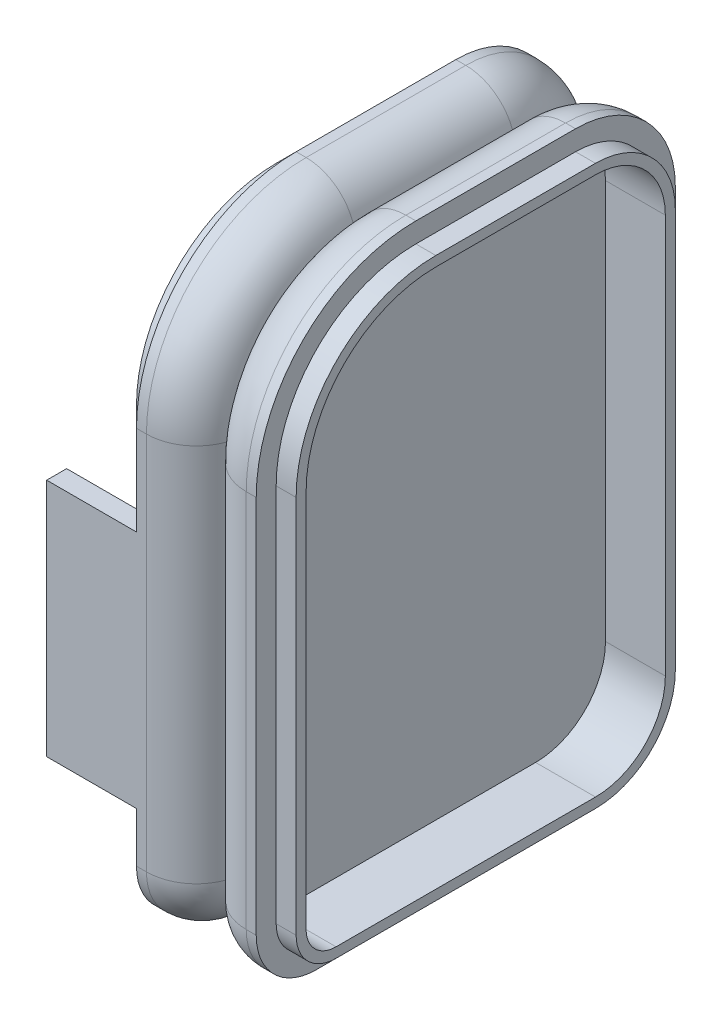
SolidWorks part; units mm, degrees
ref_plane "Спереди" through (0, 0, 0) normal (0, 0, 1) x (1, 0, 0)
ref_plane "Сверху" through (0, 0, 0) normal (0, 1, 0) x (1, 0, 0)
ref_plane "Справа" through (0, 0, 0) normal (1, 0, 0) x (0, 0, -1)
sketch "Эскиз1" plane through (0, 0, 0) normal (1, 0, 0) x (0, 0, -1)
  line L0 (2, 30) -> (40, 30) construction
  line L1 (0, 0) -> (2, 0)
  line L2 (0, 0) -> (0, 60)
  line L3 (0, 60) -> (2, 60)
  line L4 (2, 0) -> (2, 60)
  line L5 (2, 0) -> (18, 0)
  line L6 (2, 0) -> (2, 2)
  line L7 (2, 2) -> (18, 2)
  line L8 (18, 0) -> (18, 2)
  line L9 (18, 0) -> (19, 0)
  line L10 (18, 0) -> (18, 1.9)
  line L11 (18, 1.9) -> (19, 1.9)
  line L12 (19, 0) -> (19, 1.9)
  line L13 (19, 0) -> (40, 0)
  line L14 (19, 0) -> (19, 2)
  line L15 (19, 2) -> (40, 2)
  line L16 (40, 0) -> (40, 2)
  line L17 (2, 60) -> (18, 60)
  line L18 (2, 60) -> (2, 58)
  line L19 (2, 58) -> (18, 58)
  line L20 (18, 60) -> (18, 58)
  line L21 (18, 60) -> (19, 60)
  line L22 (18, 60) -> (18, 58.1)
  line L23 (18, 58.1) -> (19, 58.1)
  line L24 (19, 60) -> (19, 58.1)
  line L25 (19, 60) -> (40, 60)
  line L26 (19, 60) -> (19, 58)
  line L27 (19, 58) -> (40, 58)
  line L28 (40, 60) -> (40, 58)
  line L29 (40, 60) -> (42, 60)
  line L30 (40, 60) -> (40, 0)
  line L31 (40, 0) -> (42, 0)
  line L32 (42, 60) -> (42, 0)
  dimension "D1" = 2
  dimension "D2" = 60
  dimension "D3" = 18
  dimension "D4" = 1.9
  dimension "D5" = 1
  dimension "D6" = 21
extrude "Бобышка-Вытянуть1" add sketch "Эскиз1" against normal blind 90 contours L20 L17 L4 L19 | L24 L21 L20 L23 | L28 L25 L24 L26 L27 | L1 L4 L3 L2 | L32 L29 L28 L30 L16 L31 | L13 L16 L15 L14 L12 | L9 L12 L11 L8 | L5 L8 L7 L4 region at (0, 30, -1) region at (0, 1, -10) region at (0, 0.95, -18.5) region at (0, 59, -10) region at (0, 1, -29.5) region at (0, 59.05, -18.5) region at (0, 30, -41) region at (0, 59, -29.5)
sketch "Эскиз2" plane through (0, 0, 0) normal (1, 0, 0) x (0, 0, -1)
  line L0 (0, 0) -> (0, 60) construction
  line L1 (0, 11) -> (2, 11)
  line L2 (0, 11) -> (0, 35)
  line L3 (0, 35) -> (2, 35)
  line L4 (2, 11) -> (2, 35)
  line L5 (2, 2) -> (2, 58) construction
  line L7 (0, 0) -> (42, 0) construction
  dimension "D1" = 11
  dimension "D2" = 24
extrude "Вырез-Вытянуть1" cut sketch "Эскиз2" against normal through all
sketch "Эскиз4" plane through (-90, 0, 0) normal (-1, 0, 0) x (0, 0, 1)
  line L1 (-19, 58) -> (-18, 58)
  line L2 (-19, 58) -> (-19, 58.1)
  line L3 (-19, 58.1) -> (-18, 58.1)
  line L4 (-18, 58) -> (-18, 58.1)
  line L5 (-19, 1.9) -> (-18, 1.9)
  line L6 (-19, 1.9) -> (-19, 2)
  line L7 (-19, 2) -> (-18, 2)
  line L8 (-18, 1.9) -> (-18, 2)
extrude "Бобышка-Вытянуть2" add sketch "Эскиз4" against normal blind 3
sketch "Эскиз5" plane through (-90, 0, 0) normal (-1, 0, 0) x (0, 0, 1)
  line L1 (-2, 35) -> (0, 35)
  line L2 (-2, 35) -> (-2, 11)
  line L3 (-2, 11) -> (0, 11)
  line L4 (0, 35) -> (0, 11)
  line M1 (-2, 11) -> (-2, 2)
  line M2 (-2, 2) -> (-40, 2)
  line M3 (-40, 2) -> (-40, 58)
  line M4 (-40, 58) -> (-2, 58)
  line M5 (-2, 58) -> (-2, 35)
  line M6 (-2, 35) -> (0, 35)
  line M7 (0, 35) -> (0, 60)
  line M8 (0, 60) -> (-42, 60)
  line M9 (-42, 60) -> (-42, 0)
  line M10 (-42, 0) -> (0, 0)
  line M11 (0, 0) -> (0, 11)
  line M12 (0, 11) -> (-2, 11)
extrude "Бобышка-Вытянуть3" add sketch "Эскиз5" along normal blind 10 contours M12 M1 M2 M3 M4 M5 M6 M7 M8 M9 M10 M11 | L4 L2 M6 M12 region at (-90, 46.5, -1.2676) region at (-90, 23, -1)
sketch "Эскиз6" plane through (-100, 0, 0) normal (-1, 0, 0) x (0, 0, 1)
  line L4 (-42, 0) -> (0, 0)
  line L5 (0, 0) -> (0, 60)
  line L6 (0, 60) -> (-42, 60)
  line L7 (-42, 60) -> (-42, 0)
  line L8 (-42, 0) -> (0, 0)
  line L9 (0, 0) -> (0, 60)
  line L10 (0, 60) -> (-42, 60)
  line L11 (-42, 60) -> (-42, 0)
  dimension "D1" = 0
extrude "Бобышка-Вытянуть4" add sketch "Эскиз6" along normal blind 2
sketch "Эскиз8" plane through (0, 11, 0) normal (0, 1, 0) x (1, 0, 0)
  line L0 (-90, 2) -> (0, 2) construction
  line L1 (-90, 0) -> (-80, 0)
  line L2 (-90, 0) -> (-90, 2)
  line L3 (-90, 2) -> (-80, 2)
  line L4 (-80, 0) -> (-80, 2)
  dimension "D1" = 10
extrude "Бобышка-Вытянуть5" add sketch "Эскиз8" along normal up to next
fillet "Скругление1" radius 14 1 edges at (-50, 58, -2)
fillet "Скругление2" radius 16 1 edges at (-51, 60, 0)
fillet "Скругление4" radius 8 2 edges at (-50, 58, -40) (-50, 2, -40)
fillet "Скругление5" radius 10 2 edges at (-51, 60, -42) (-51, 0, -42)
fillet "Скругление6" radius 4 1 edges at (-50, 2, -2)
fillet "Скругление7" radius 6 1 edges at (-51, 0, 0)
fillet "Скругление8" radius 5 8 edges at (-102, 25, 0) (-102, 1.7574, -1.7574) (-102, 0, -19) (-102, 2.9289, -39.0711) (-102, 30, -42) (-102, 57.0711, -39.0711) (-102, 60, -24) (-102, 55.3137, -4.6863)
fillet "Скругление9" radius 1 8 edges at (-100, 3.1716, -3.1716) (-100, 25, -2) (-100, 53.8995, -6.1005) (-100, 58, -24) (-100, 55.6569, -37.6569) (-100, 30, -40) (-100, 4.3431, -37.6569) (-100, 2, -19)
sketch "Эскиз9" plane through (0, 0, 0) normal (1, 0, 0) x (0, 0, -1)
  line L20 (0, 11) -> (0, 6)
  line L21 (6, 0) -> (32, 0)
  line L22 (42, 10) -> (42, 50)
  line L23 (32, 60) -> (16, 60)
  line L24 (0, 44) -> (0, 35)
  line L25 (0, 35) -> (2, 35)
  line L26 (2, 35) -> (2, 44)
  line L27 (16, 58) -> (18, 58)
  line L28 (18, 58) -> (18, 58.1)
  line L29 (18, 58.1) -> (19, 58.1)
  line L30 (19, 58.1) -> (19, 58)
  line L31 (19, 58) -> (32, 58)
  line L32 (40, 50) -> (40, 10)
  line L33 (32, 2) -> (19, 2)
  line L34 (19, 2) -> (19, 1.9)
  line L35 (19, 1.9) -> (18, 1.9)
  line L36 (18, 1.9) -> (18, 2)
  line L37 (18, 2) -> (6, 2)
  line L38 (2, 6) -> (2, 11)
  line L39 (2, 11) -> (0, 11)
  line L40 (0, 11) -> (0, 6)
  line L41 (6, 0) -> (32, 0)
  line L42 (42, 10) -> (42, 50)
  line L43 (32, 60) -> (16, 60)
  line L44 (0, 44) -> (0, 35)
  line L45 (0, 35) -> (2, 35)
  line L46 (2, 35) -> (2, 44)
  line L47 (16, 58) -> (18, 58)
  line L48 (18, 58) -> (18, 58.1)
  line L49 (18, 58.1) -> (19, 58.1)
  line L50 (19, 58.1) -> (19, 58)
  line L51 (19, 58) -> (32, 58)
  line L52 (40, 50) -> (40, 10)
  line L53 (32, 2) -> (19, 2)
  line L54 (19, 2) -> (19, 1.9)
  line L55 (19, 1.9) -> (18, 1.9)
  line L56 (18, 1.9) -> (18, 2)
  line L57 (18, 2) -> (6, 2)
  line L58 (2, 6) -> (2, 11)
  line L59 (2, 11) -> (0, 11)
  arc A8 (0, 6) -> (6, 0) centre (6, 6) ccw
  arc A9 (32, 0) -> (42, 10) centre (32, 10) ccw
  arc A10 (42, 50) -> (32, 60) centre (32, 50) ccw
  arc A11 (16, 60) -> (0, 44) centre (16, 44) ccw
  arc A12 (16, 58) -> (2, 44) centre (16, 44) ccw
  arc A13 (40, 50) -> (32, 58) centre (32, 50) ccw
  arc A14 (32, 2) -> (40, 10) centre (32, 10) ccw
  arc A15 (2, 6) -> (6, 2) centre (6, 6) ccw
  arc A16 (0, 6) -> (6, 0) centre (6, 6) ccw
  arc A17 (32, 0) -> (42, 10) centre (32, 10) ccw
  arc A18 (42, 50) -> (32, 60) centre (32, 50) ccw
  arc A19 (16, 60) -> (0, 44) centre (16, 44) ccw
  arc A20 (16, 58) -> (2, 44) centre (16, 44) ccw
  arc A21 (40, 50) -> (32, 58) centre (32, 50) ccw
  arc A22 (32, 2) -> (40, 10) centre (32, 10) ccw
  arc A23 (2, 6) -> (6, 2) centre (6, 6) ccw
  dimension "D1" = 0
extrude "Вырез-Вытянуть2" cut sketch "Эскиз9" against normal up to surface (80 mm away) up to face at (-80, 23, -1)
sketch "Эскиз10" plane through (-80, 0, 0) normal (1, 0, 0) x (0, 0, -1)
  line L4 (0, 44) -> (0, 6)
  line L5 (6, 0) -> (32, 0)
  line L6 (42, 10) -> (42, 50)
  line L7 (32, 60) -> (16, 60)
  line L8 (0, 44) -> (0, 6)
  line L9 (6, 0) -> (32, 0)
  line L10 (42, 10) -> (42, 50)
  line L11 (32, 60) -> (16, 60)
  arc A4 (16, 60) -> (0, 44) centre (16, 44) ccw
  arc A5 (0, 6) -> (6, 0) centre (6, 6) ccw
  arc A6 (32, 0) -> (42, 10) centre (32, 10) ccw
  arc A7 (42, 50) -> (32, 60) centre (32, 50) ccw
  arc A8 (16, 60) -> (0, 44) centre (16, 44) ccw
  arc A9 (0, 6) -> (6, 0) centre (6, 6) ccw
  arc A10 (32, 0) -> (42, 10) centre (32, 10) ccw
  arc A11 (42, 50) -> (32, 60) centre (32, 50) ccw
  dimension "D1" = 0
extrude "Вырез-Вытянуть3" cut sketch "Эскиз10" against normal blind 16
sketch "Эскиз12" plane through (-96, 0, 0) normal (1, 0, 0) x (0, 0, -1)
  line L0 (2, 44) -> (2, 6) construction
  line L1 (32, 2) -> (6, 2) construction
  line L2 (40, 10) -> (40, 50) construction
  line L3 (32, 58) -> (16, 58) construction
  line L4 (2, 44) -> (2, 6)
  line L5 (32, 2) -> (6, 2)
  line L6 (40, 10) -> (40, 50)
  line L7 (32, 58) -> (16, 58)
  line L8 (3, 44) -> (3, 6)
  line L9 (32, 3) -> (6, 3)
  line L10 (39, 10) -> (39, 50)
  line L11 (32, 57) -> (16, 57)
  arc A0 (2, 6) -> (6, 2) centre (6, 6) ccw construction
  arc A1 (32, 2) -> (40, 10) centre (32, 10) ccw construction
  arc A2 (40, 50) -> (32, 58) centre (32, 50) ccw construction
  arc A3 (16, 58) -> (2, 44) centre (16, 44) ccw construction
  arc A4 (2, 6) -> (6, 2) centre (6, 6) ccw
  arc A5 (32, 2) -> (40, 10) centre (32, 10) ccw
  arc A6 (40, 50) -> (32, 58) centre (32, 50) ccw
  arc A7 (16, 58) -> (2, 44) centre (16, 44) ccw
  arc A8 (16, 57) -> (3, 44) centre (16, 44) ccw
  arc A9 (3, 6) -> (6, 3) centre (6, 6) ccw
  arc A10 (32, 3) -> (39, 10) centre (32, 10) ccw
  arc A11 (39, 50) -> (32, 57) centre (32, 50) ccw
  dimension "D1" = 1
extrude "Бобышка-Вытянуть7" add sketch "Эскиз12" against normal up to surface (4 mm away) and the other way blind 2 up to face at (-100, 29.0089, -21.1982)
mirror "Зеркальное отражение1" about plane through (-102, 0, 0) normal (-1, 0, 0) of bodies 119 117
sketch "Эскиз13" plane through (-108, 0, 0) normal (-1, 0, 0) x (0, 0, 1)
  line L0 (-2, 44) -> (-2, 6) construction
  line L1 (-2, 35) -> (0, 35)
  line L2 (-2, 35) -> (-2, 11)
  line L3 (-2, 11) -> (0, 11)
  line L4 (0, 35) -> (0, 11)
  line L5 (0, 44) -> (0, 6) construction
  line L6 (-6, 0) -> (-32, 0) construction
  dimension "D1" = 11
  dimension "D2" = 24
extrude "Бобышка-Вытянуть8" add sketch "Эскиз13" along normal blind 9
sketch "Эскиз14" plane through (-104, 0, 0) normal (-1, 0, 0) x (0, 0, 1)
  line L0 (-42, 10) -> (-42, 50) construction
  line L1 (-35, 40) -> (-33.5, 40)
  line L2 (-35, 40) -> (-35, 45)
  line L3 (-35, 45) -> (-33.5, 45)
  line L4 (-33.5, 40) -> (-33.5, 45)
  line L5 (-6, 0) -> (-32, 0) construction
  dimension "D1" = 5
  dimension "D2" = 1.5
  dimension "D3" = 7
  dimension "D4" = 40
extrude "Вырез-Вытянуть4" cut sketch "Эскиз14" against normal through all
sketch "Эскиз15" plane through (-102, 0, 0) normal (1, 0, 0) x (0, 0, -1)
  line L0 (32, 60) -> (16, 60) construction
  line L2 (0, 44) -> (0, 6) construction
  circle A0 centre (10.4, 47) radius 1.5
  dimension "D3" = 3
  dimension "D1" = 13
  dimension "D2" = 10.4
extrude "Вырез-Вытянуть5" cut sketch "Эскиз15" against normal through all
equation "\"СТЕНКИ\"= 2"
equation "\"D1@Эскиз1\"=\"СТЕНКИ\""
equation "\"D1@Бобышка-Вытянуть4\"=\"СТЕНКИ\""
equation "\"ъ\"=15"
